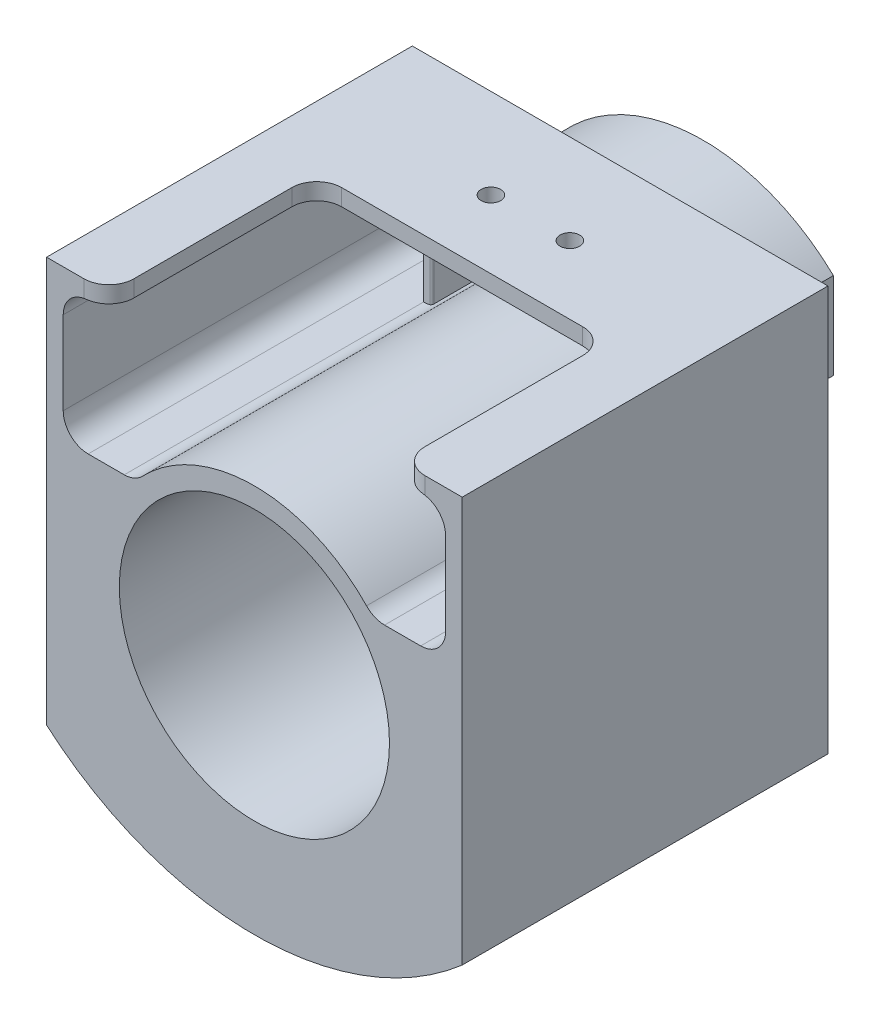
SolidWorks part; units mm, degrees
ref_plane "Front Plane" through (0, 0, 0) normal (0, 0, 1) x (1, 0, 0)
ref_plane "Top Plane" through (0, 0, 0) normal (0, 1, 0) x (1, 0, 0)
ref_plane "Right Plane" through (0, 0, 0) normal (1, 0, 0) x (0, 0, -1)
sketch "Sketch1" plane through (0, 0, 0) normal (0, 0, 1) x (1, 0, 0)
  line L1 (0, 0) -> (0, -38.1) construction
  line L2 (-25, 0) -> (-25, -28.7508)
  line L3 (25, 0) -> (25, -28.7508)
  line L4 (-25, 0) -> (-25, 20)
  line L5 (-25, 20) -> (25, 20)
  line L6 (25, 20) -> (25, 0)
  arc A0 (-25, -28.7508) -> (25, -28.7508) centre (0, 0) ccw
  dimension "D1" = 76.2
  dimension "D2" = 50
  dimension "D3" = 20
extrude "Boss-Extrude2" add sketch "Sketch1" along normal blind 44 from offset 6
sketch "Sketch2" plane through (0, 0, 50) normal (0, 0, 1) x (1, 0, 0)
  line L6 (0, 6.25) -> (0, -26.25) construction
  circle A0 centre (0, -10) radius 16.25
  dimension "D2" = 32.5
  dimension "D1" = 10
extrude "Cut-Extrude1" cut sketch "Sketch2" against normal through all both
sketch "Sketch4" plane through (0, 0, 50) normal (0, 0, 1) x (1, 0, 0)
  line L0 (-23, 18) -> (23, 18)
  line L3 (0, 20) -> (0, 6.25) construction
  line L4 (25, 20) -> (-25, 20) construction
  line L5 (23, 2) -> (14.3178, 2)
  line L6 (-23, 18) -> (-23, 2)
  line L7 (-23, 2) -> (-14.3178, 2)
  line L8 (-25, 20) -> (-25, -28.7508) construction
  line L9 (23, 18) -> (23, 2)
  circle A2 centre (0, -10) radius 16.25 construction
  arc A3 (14.3178, 2) -> (-14.3178, 2) centre (0, -10) ccw
  point P2 (0, 13.125)
  point P14 (0, 18)
  dimension "D1" = 37.3631
  dimension "D2" = 2
  dimension "D3" = 2
  dimension "D4" = 16
extrude "Cut-Extrude3" cut sketch "Sketch4" against normal through all
fillet "Fillet1" radius 3 6 edges at (23, 18, 28) (23, 2, 28) (14.3178, 2, 28) (-14.3178, 2, 28) (-23, 2, 28) (-23, 18, 28)
sketch "Sketch5" plane through (0, 20, 0) normal (0, 1, 0) x (1, 0, 0)
  line L0 (25, -50) -> (-25, -50) construction
  line L1 (-17.5, -50) -> (17.5, -50)
  line L2 (-17.5, -50) -> (-17.5, -25)
  line L3 (-17.5, -25) -> (17.5, -25)
  line L4 (17.5, -50) -> (17.5, -25)
  line L5 (0, 0) -> (0, -50) construction
  dimension "D1" = 35
  dimension "D2" = 25
extrude "Cut-Extrude4" cut sketch "Sketch5" against normal blind 10
fillet "Fillet2" radius 3 4 edges at (17.5, 19, 50) (17.5, 19, 25) (-17.5, 19, 25) (-17.5, 19, 50)
ref_plane "Plane1" through (0, 0, 14) normal (0, 0, 1) x (1, 0, 0)
sketch "Sketch6" plane through (0, 0, 14) normal (0, 0, 1) x (1, 0, 0)
  line L0 (0, -10) -> (0, 3) construction
  line L1 (0, -10) -> (-4.4463, 2.216) construction
  circle A1 centre (0, -10) radius 16.25 construction
  circle A3 centre (0, -10) radius 9.5
  circle A8 centre (0, -10) radius 16.25
  circle A9 centre (0, -10) radius 13 construction
  circle A10 centre (-4.4463, 2.216) radius 1.65
  circle A11 centre (12.216, -5.5537) radius 1.65
  circle A12 centre (4.4463, -22.216) radius 1.65
  circle A13 centre (-12.216, -14.4463) radius 1.65
  dimension "D1" = 19
  dimension "D6" = 13
  dimension "D2" = 3.5
  dimension "D3" = 3.3
  dimension "D4" = 20
  dimension "D5" = 4
extrude "Boss-Extrude3" add sketch "Sketch6" against normal blind 5
sketch "Sketch7" plane through (0, 0, 0) normal (1, 0, 0) x (0, 0, -1)
  circle A0 centre (-44, -32) radius 2.25
  circle A1 centre (-14, -32) radius 2.25
  dimension "D3" = 4.5
  dimension "D1" = 32
  dimension "D2" = 14
  dimension "D4" = 30
extrude "Cut-Extrude5" cut sketch "Sketch7" against normal through all both and the other way through all
sketch "Sketch8" plane through (0, 20, 0) normal (0, 1, 0) x (1, 0, 0)
  line L0 (0, -6) -> (0, -25) construction
  line L1 (25, -6) -> (-25, -6) construction
  line L2 (14.5, -25) -> (-14.5, -25) construction
  circle A0 centre (-4.75, -16.8) radius 1.175
  circle A1 centre (4.75, -16.8) radius 1.175
  dimension "D1" = 2.35
  dimension "D2" = 9.5
  dimension "D3" = 10.8
extrude "Cut-Extrude6" cut sketch "Sketch8" against normal up to next contours A0 | A1
sketch "Sketch9" plane through (0, 0, 50) normal (0, 0, 1) x (1, 0, 0)
  line L0 (0, -28.5) -> (0, -5) construction
  line L1 (0, -10) -> (0, -28.5) construction
  line L2 (-15.6553, 2) -> (-15.6553, 11.4123)
  line L3 (15.6553, 2) -> (15.6553, 11.4123)
  line L4 (0, 8.6815) -> (0, 17.6815) construction
  line L5 (-14.6553, 2.1716) -> (-14.6553, 10.5325)
  line L6 (14.6553, 2.1716) -> (14.6553, 10.5325)
  line L7 (-15.6553, 2) -> (-15.6553, 1)
  line L8 (15.6553, 2) -> (15.6553, 1)
  line L9 (14.6553, 2) -> (14.6553, 10.9784) construction
  line L10 (-14.6553, 2) -> (-14.6553, 10.9784) construction
  arc A0 (13.4892, 2.9245) -> (-13.4892, 2.9245) centre (0, -10) ccw construction
  arc A1 (13.4892, 2.9245) -> (-13.4892, 2.9245) centre (0, -10) ccw
  arc A3 (-15.6553, 11.4123) -> (15.6553, 11.4123) centre (0, -5) cw
  arc A4 (13.4892, 2.9245) -> (15.6553, 2) centre (15.6553, 5) ccw construction
  arc A5 (-15.6553, 2) -> (-13.4892, 2.9245) centre (-15.6553, 5) ccw construction
  arc A6 (13.4892, 2.9245) -> (15.6553, 2) centre (15.6553, 5) ccw
  arc A7 (-15.6553, 2) -> (-13.4892, 2.9245) centre (-15.6553, 5) ccw
  arc A8 (12.7671, 2.2327) -> (15.6553, 1) centre (15.6553, 5) ccw
  arc A9 (12.7671, 2.2327) -> (-12.7671, 2.2327) centre (0, -10) ccw
  arc A10 (-15.6553, 1) -> (-12.7671, 2.2327) centre (-15.6553, 5) ccw
  arc A11 (-14.3156, 11.2835) -> (14.3156, 11.2835) centre (0, -5) cw
  arc A12 (-14.6553, 10.9784) -> (14.6553, 10.9784) centre (0, -5) cw construction
  arc A13 (14.6553, 10.5325) -> (14.3156, 11.2835) centre (13.6553, 10.5325) ccw
  arc A14 (-14.6553, 10.5325) -> (-14.3156, 11.2835) centre (-13.6553, 10.5325) cw
  dimension "D1" = 9
  dimension "D2" = 1
  dimension "D4" = 1
  dimension "Ring Gear Outer Dia to Center" = 23.5
  dimension "Pinion to Ring Gear Outer Diameter" = 18.5
  dimension "D3" = 1
extrude "Boss-Extrude4" add sketch "Sketch9" along normal blind 8 and the other way blind 10 from surface contours L5 A11 L6 L2 L3 A3 A6 | L7 A10 A9 A8 L8 L2 L3 A6 region at (-15.0935, 1.7255, 50) region at (-15.3051, 6.7061, 50) starting at face at (0, 7.9303, 6)
fillet "Fillet5" radius 0.25 8 edges at (14.0281, 2.4797, -4) (-14.0281, 2.4797, -4) (14.6553, 6.352, -4) (14.5664, 10.9446, -4) (-14.6553, 6.352, -4) (-14.5664, 10.9446, -4) (0, 8.6815, -4) (0, 16.6815, -4)
fillet "Fillet6" radius 0.25 5 edges at (14.6553, 6.352, 14) (14.5664, 10.9446, 14) (-14.6553, 6.352, 14) (-14.5664, 10.9446, 14) (0, 16.6815, 14)
